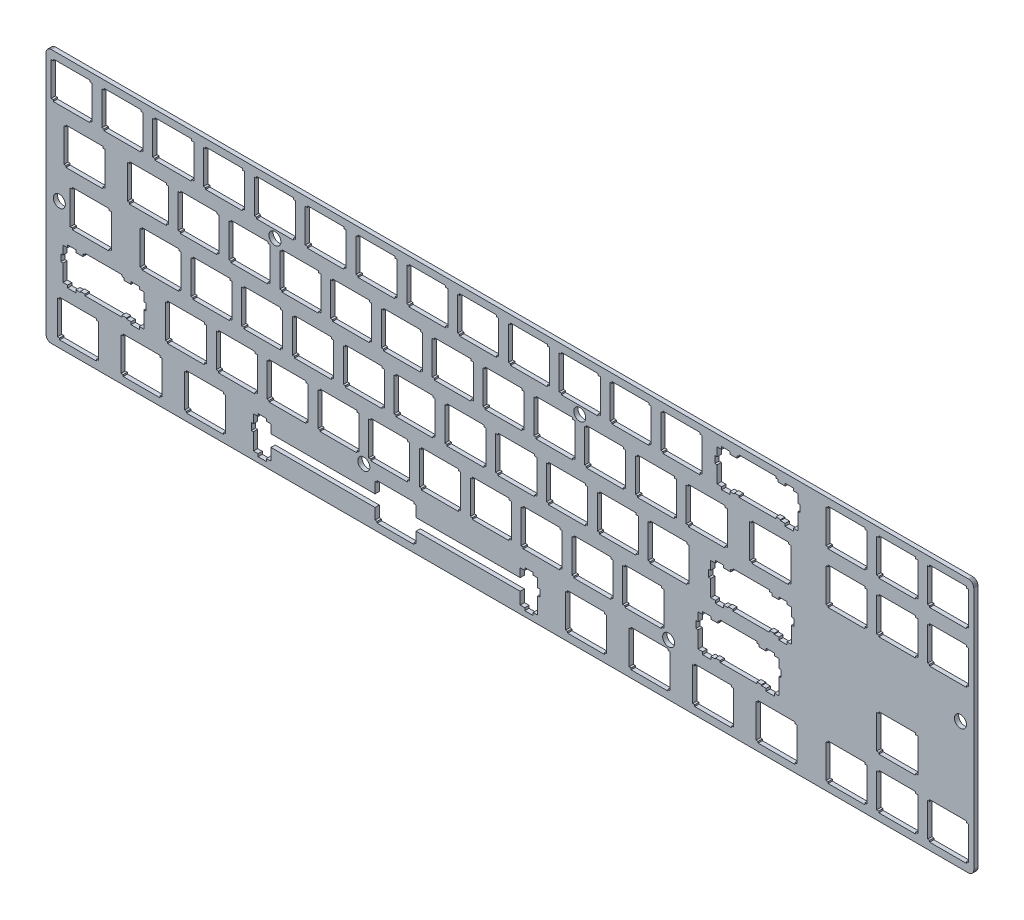
SolidWorks part; units mm, degrees
material "Brass"
ref_plane "Front Plane" through (0, 0, 0) normal (0, 0, 1) x (1, 0, 0)
ref_plane "Top Plane" through (0, 0, 0) normal (0, 1, 0) x (1, 0, 0)
ref_plane "Right Plane" through (0, 0, 0) normal (1, 0, 0) x (0, 0, -1)
sketch "Model" plane through (0, 0, 0) normal (0, 0, 1) x (1, 0, 0)
  line L0 (148.8206, 120.9391) -> (148.8206, 120.3396)
  line L1 (148.8206, 120.3396) -> (148.0216, 120.3396)
  line L2 (148.0216, 120.3396) -> (148.0216, 116.2386)
  line L3 (148.0216, 116.2386) -> (108.9957, 116.2386)
  line L4 (108.9957, 116.2386) -> (108.9957, 119.4687)
  line L5 (108.9957, 119.4687) -> (107.2716, 119.4687)
  line L6 (107.2716, 119.4687) -> (107.2716, 120.3879)
  line L7 (107.2716, 120.3879) -> (104.1711, 120.3879)
  line L8 (104.1711, 120.3879) -> (104.1711, 119.4687)
  line L9 (104.1711, 119.4687) -> (102.4456, 119.4687)
  line L10 (102.4456, 119.4687) -> (102.4456, 116.2386)
  line L11 (102.4456, 116.2386) -> (101.6216, 116.2386)
  line L12 (101.6216, 116.2386) -> (101.6216, 113.6383)
  line L13 (101.6216, 113.6383) -> (102.4456, 113.6383)
  line L14 (102.4456, 113.6383) -> (102.4456, 107.3696)
  line L15 (102.4456, 107.3696) -> (104.1711, 107.3696)
  line L16 (104.1711, 107.3696) -> (104.1711, 106.3884)
  line L17 (104.1711, 106.3884) -> (107.2716, 106.3884)
  line L18 (107.2716, 106.3884) -> (107.2716, 107.3696)
  line L19 (107.2716, 107.3696) -> (108.9957, 107.3696)
  line L20 (108.9957, 107.3696) -> (108.9957, 111.8386)
  line L21 (108.9957, 111.8386) -> (148.0216, 111.8386)
  line L22 (148.0216, 111.8386) -> (148.0216, 107.7389)
  line L23 (148.0216, 107.7389) -> (148.8206, 107.7389)
  line L24 (148.8206, 107.7389) -> (148.8206, 107.1381)
  line L25 (148.8206, 107.1381) -> (162.6206, 107.1381)
  line L26 (162.6206, 107.1381) -> (162.6206, 107.7389)
  line L27 (162.6206, 107.7389) -> (163.4216, 107.7389)
  line L28 (163.4216, 107.7389) -> (163.4216, 111.8386)
  line L29 (163.4216, 111.8386) -> (202.4456, 111.8386)
  line L30 (202.4456, 111.8386) -> (202.4456, 107.3696)
  line L31 (202.4456, 107.3696) -> (204.1716, 107.3696)
  line L32 (204.1716, 107.3696) -> (204.1716, 106.3884)
  line L33 (204.1716, 106.3884) -> (207.2716, 106.3884)
  line L34 (207.2716, 106.3884) -> (207.2716, 107.3696)
  line L35 (207.2716, 107.3696) -> (208.9956, 107.3696)
  line L36 (208.9956, 107.3696) -> (208.9956, 113.6383)
  line L37 (208.9956, 113.6383) -> (209.8206, 113.6383)
  line L38 (209.8206, 113.6383) -> (209.8206, 116.2386)
  line L39 (209.8206, 116.2386) -> (208.9956, 116.2386)
  line L40 (208.9956, 116.2386) -> (208.9956, 119.4687)
  line L41 (208.9956, 119.4687) -> (207.2716, 119.4687)
  line L42 (207.2716, 119.4687) -> (207.2716, 120.3879)
  line L43 (207.2716, 120.3879) -> (204.1716, 120.3879)
  line L44 (204.1716, 120.3879) -> (204.1716, 119.4687)
  line L45 (204.1716, 119.4687) -> (202.4456, 119.4687)
  line L46 (202.4456, 119.4687) -> (202.4456, 116.2386)
  line L47 (202.4456, 116.2386) -> (163.4216, 116.2386)
  line L48 (163.4216, 116.2386) -> (163.4216, 120.3396)
  line L49 (163.4216, 120.3396) -> (162.6206, 120.3396)
  line L50 (162.6206, 120.3396) -> (162.6206, 120.9391)
  line L51 (162.6206, 120.9391) -> (148.8206, 120.9391)
  line L52 (355.9896, 120.9391) -> (355.9896, 120.3396)
  line L53 (355.9896, 120.3396) -> (355.1906, 120.3396)
  line L54 (355.1906, 120.3396) -> (355.1906, 107.7389)
  line L55 (355.1906, 107.7389) -> (355.9896, 107.7389)
  line L56 (355.9896, 107.7389) -> (355.9896, 107.1381)
  line L57 (355.9896, 107.1381) -> (369.7906, 107.1381)
  line L58 (369.7906, 107.1381) -> (369.7906, 107.7389)
  line L59 (369.7906, 107.7389) -> (370.5896, 107.7389)
  line L60 (370.5896, 107.7389) -> (370.5896, 120.3396)
  line L61 (370.5896, 120.3396) -> (369.7906, 120.3396)
  line L62 (369.7906, 120.3396) -> (369.7906, 120.9391)
  line L63 (369.7906, 120.9391) -> (355.9896, 120.9391)
  line L64 (336.9396, 120.9391) -> (336.9396, 120.3396)
  line L65 (336.9396, 120.3396) -> (336.1406, 120.3396)
  line L66 (336.1406, 120.3396) -> (336.1406, 107.7389)
  line L67 (336.1406, 107.7389) -> (336.9396, 107.7389)
  line L68 (336.9396, 107.7389) -> (336.9396, 107.1381)
  line L69 (336.9396, 107.1381) -> (350.7406, 107.1381)
  line L70 (350.7406, 107.1381) -> (350.7406, 107.7389)
  line L71 (350.7406, 107.7389) -> (351.5396, 107.7389)
  line L72 (351.5396, 107.7389) -> (351.5396, 120.3396)
  line L73 (351.5396, 120.3396) -> (350.7406, 120.3396)
  line L74 (350.7406, 120.3396) -> (350.7406, 120.9391)
  line L75 (350.7406, 120.9391) -> (336.9396, 120.9391)
  line L76 (317.8896, 120.9391) -> (317.8896, 120.3396)
  line L77 (317.8896, 120.3396) -> (317.0906, 120.3396)
  line L78 (317.0906, 120.3396) -> (317.0906, 107.7389)
  line L79 (317.0906, 107.7389) -> (317.8896, 107.7389)
  line L80 (317.8896, 107.7389) -> (317.8896, 107.1381)
  line L81 (317.8896, 107.1381) -> (331.6906, 107.1381)
  line L82 (331.6906, 107.1381) -> (331.6906, 107.7389)
  line L83 (331.6906, 107.7389) -> (332.4896, 107.7389)
  line L84 (332.4896, 107.7389) -> (332.4896, 120.3396)
  line L85 (332.4896, 120.3396) -> (331.6906, 120.3396)
  line L86 (331.6906, 120.3396) -> (331.6906, 120.9391)
  line L87 (331.6906, 120.9391) -> (317.8896, 120.9391)
  line L88 (291.6956, 120.9391) -> (291.6956, 120.3396)
  line L89 (291.6956, 120.3396) -> (290.8966, 120.3396)
  line L90 (290.8966, 120.3396) -> (290.8966, 107.7389)
  line L91 (290.8966, 107.7389) -> (291.6956, 107.7389)
  line L92 (291.6956, 107.7389) -> (291.6956, 107.1381)
  line L93 (291.6956, 107.1381) -> (305.4956, 107.1381)
  line L94 (305.4956, 107.1381) -> (305.4956, 107.7389)
  line L95 (305.4956, 107.7389) -> (306.2966, 107.7389)
  line L96 (306.2966, 107.7389) -> (306.2966, 120.3396)
  line L97 (306.2966, 120.3396) -> (305.4956, 120.3396)
  line L98 (305.4956, 120.3396) -> (305.4956, 120.9391)
  line L99 (305.4956, 120.9391) -> (291.6956, 120.9391)
  line L100 (267.8846, 120.9391) -> (267.8846, 120.3396)
  line L101 (267.8846, 120.3396) -> (267.0846, 120.3396)
  line L102 (267.0846, 120.3396) -> (267.0846, 107.7389)
  line L103 (267.0846, 107.7389) -> (267.8846, 107.7389)
  line L104 (267.8846, 107.7389) -> (267.8846, 107.1381)
  line L105 (267.8846, 107.1381) -> (281.6846, 107.1381)
  line L106 (281.6846, 107.1381) -> (281.6846, 107.7389)
  line L107 (281.6846, 107.7389) -> (282.4836, 107.7389)
  line L108 (282.4836, 107.7389) -> (282.4836, 120.3396)
  line L109 (282.4836, 120.3396) -> (281.6846, 120.3396)
  line L110 (281.6846, 120.3396) -> (281.6846, 120.9391)
  line L111 (281.6846, 120.9391) -> (267.8846, 120.9391)
  line L112 (244.0706, 120.9391) -> (244.0706, 120.3396)
  line L113 (244.0706, 120.3396) -> (243.2716, 120.3396)
  line L114 (243.2716, 120.3396) -> (243.2716, 107.7389)
  line L115 (243.2716, 107.7389) -> (244.0706, 107.7389)
  line L116 (244.0706, 107.7389) -> (244.0706, 107.1381)
  line L117 (244.0706, 107.1381) -> (257.8706, 107.1381)
  line L118 (257.8706, 107.1381) -> (257.8706, 107.7389)
  line L119 (257.8706, 107.7389) -> (258.6716, 107.7389)
  line L120 (258.6716, 107.7389) -> (258.6716, 120.3396)
  line L121 (258.6716, 120.3396) -> (257.8706, 120.3396)
  line L122 (257.8706, 120.3396) -> (257.8706, 120.9391)
  line L123 (257.8706, 120.9391) -> (244.0706, 120.9391)
  line L124 (220.2596, 120.9391) -> (220.2596, 120.3396)
  line L125 (220.2596, 120.3396) -> (219.4596, 120.3396)
  line L126 (219.4596, 120.3396) -> (219.4596, 107.7389)
  line L127 (219.4596, 107.7389) -> (220.2596, 107.7389)
  line L128 (220.2596, 107.7389) -> (220.2596, 107.1381)
  line L129 (220.2596, 107.1381) -> (234.0596, 107.1381)
  line L130 (234.0596, 107.1381) -> (234.0596, 107.7389)
  line L131 (234.0596, 107.7389) -> (234.8586, 107.7389)
  line L132 (234.8586, 107.7389) -> (234.8586, 120.3396)
  line L133 (234.8586, 120.3396) -> (234.0596, 120.3396)
  line L134 (234.0596, 120.3396) -> (234.0596, 120.9391)
  line L135 (234.0596, 120.9391) -> (220.2596, 120.9391)
  line L136 (77.3847, 120.9391) -> (77.3847, 120.3396)
  line L137 (77.3847, 120.3396) -> (76.5842, 120.3396)
  line L138 (76.5842, 120.3396) -> (76.5842, 107.7389)
  line L139 (76.5842, 107.7389) -> (77.3847, 107.7389)
  line L140 (77.3847, 107.7389) -> (77.3847, 107.1381)
  line L141 (77.3847, 107.1381) -> (91.1843, 107.1381)
  line L142 (91.1843, 107.1381) -> (91.1843, 107.7389)
  line L143 (91.1843, 107.7389) -> (91.9837, 107.7389)
  line L144 (91.9837, 107.7389) -> (91.9837, 120.3396)
  line L145 (91.9837, 120.3396) -> (91.1843, 120.3396)
  line L146 (91.1843, 120.3396) -> (91.1843, 120.9391)
  line L147 (91.1843, 120.9391) -> (77.3847, 120.9391)
  line L148 (53.5708, 120.9391) -> (53.5708, 120.3396)
  line L149 (53.5708, 120.3396) -> (52.7716, 120.3396)
  line L150 (52.7716, 120.3396) -> (52.7716, 107.7389)
  line L151 (52.7716, 107.7389) -> (53.5708, 107.7389)
  line L152 (53.5708, 107.7389) -> (53.5708, 107.1381)
  line L153 (53.5708, 107.1381) -> (67.3704, 107.1381)
  line L154 (67.3704, 107.1381) -> (67.3704, 107.7389)
  line L155 (67.3704, 107.7389) -> (68.1712, 107.7389)
  line L156 (68.1712, 107.7389) -> (68.1712, 120.3396)
  line L157 (68.1712, 120.3396) -> (67.3704, 120.3396)
  line L158 (67.3704, 120.3396) -> (67.3704, 120.9391)
  line L159 (67.3704, 120.9391) -> (53.5708, 120.9391)
  line L160 (29.7597, 120.9391) -> (29.7597, 120.3396)
  line L161 (29.7597, 120.3396) -> (28.959, 120.3396)
  line L162 (28.959, 120.3396) -> (28.959, 107.7389)
  line L163 (28.959, 107.7389) -> (29.7597, 107.7389)
  line L164 (29.7597, 107.7389) -> (29.7597, 107.1381)
  line L165 (29.7597, 107.1381) -> (43.5594, 107.1381)
  line L166 (43.5594, 107.1381) -> (43.5594, 107.7389)
  line L167 (43.5594, 107.7389) -> (44.3586, 107.7389)
  line L168 (44.3586, 107.7389) -> (44.3586, 120.3396)
  line L169 (44.3586, 120.3396) -> (43.5594, 120.3396)
  line L170 (43.5594, 120.3396) -> (43.5594, 120.9391)
  line L171 (43.5594, 120.9391) -> (29.7597, 120.9391)
  line L172 (277.4086, 139.9906) -> (277.4086, 139.3898)
  line L173 (277.4086, 139.3898) -> (276.6096, 139.3898)
  line L174 (276.6096, 139.3898) -> (276.6096, 138.5187)
  line L175 (275.6846, 138.5187) -> (273.9596, 138.5187)
  line L176 (273.9596, 138.5187) -> (273.9596, 139.4378)
  line L177 (273.9596, 139.4378) -> (270.8586, 139.4378)
  line L178 (270.8586, 139.4378) -> (270.8586, 138.5187)
  line L179 (270.8586, 138.5187) -> (269.1346, 138.5187)
  line L180 (269.1346, 138.5187) -> (269.1346, 135.2886)
  line L181 (269.1346, 135.2886) -> (268.3086, 135.2886)
  line L182 (268.3086, 135.2886) -> (268.3086, 132.6882)
  line L183 (268.3086, 132.6882) -> (269.1346, 132.6882)
  line L184 (269.1346, 132.6882) -> (269.1346, 126.4182)
  line L185 (269.1346, 126.4182) -> (270.8586, 126.4182)
  line L186 (270.8586, 126.4182) -> (270.8586, 125.4384)
  line L187 (270.8586, 125.4384) -> (273.9596, 125.4384)
  line L188 (273.9596, 125.4384) -> (273.9596, 126.4182)
  line L189 (273.9596, 126.4182) -> (275.6846, 126.4182)
  line L190 (275.6846, 126.4182) -> (275.6846, 126.7888)
  line L191 (276.6096, 126.7888) -> (277.4086, 126.7888)
  line L192 (277.4086, 126.7888) -> (277.4086, 126.188)
  line L193 (277.4086, 126.188) -> (291.2096, 126.188)
  line L194 (291.2096, 126.188) -> (291.2096, 126.7888)
  line L195 (291.2096, 126.7888) -> (292.0086, 126.7888)
  line L196 (292.9346, 126.7888) -> (292.9346, 126.4182)
  line L197 (292.9346, 126.4182) -> (294.6586, 126.4182)
  line L198 (294.6586, 126.4182) -> (294.6586, 125.4384)
  line L199 (294.6586, 125.4384) -> (297.7596, 125.4384)
  line L200 (297.7596, 125.4384) -> (297.7596, 126.4182)
  line L201 (297.7596, 126.4182) -> (299.4846, 126.4182)
  line L202 (299.4846, 126.4182) -> (299.4846, 132.6882)
  line L203 (299.4846, 132.6882) -> (300.3086, 132.6882)
  line L204 (300.3086, 132.6882) -> (300.3086, 135.2886)
  line L205 (300.3086, 135.2886) -> (299.4846, 135.2886)
  line L206 (299.4846, 135.2886) -> (299.4846, 138.5187)
  line L207 (299.4846, 138.5187) -> (297.7596, 138.5187)
  line L208 (297.7596, 138.5187) -> (297.7596, 139.4378)
  line L209 (297.7596, 139.4378) -> (294.6586, 139.4378)
  line L210 (294.6586, 139.4378) -> (294.6586, 138.5187)
  line L211 (294.6586, 138.5187) -> (292.9346, 138.5187)
  line L212 (292.0086, 138.5187) -> (292.0086, 139.3898)
  line L213 (292.0086, 139.3898) -> (291.2096, 139.3898)
  line L214 (291.2096, 139.3898) -> (291.2096, 139.9906)
  line L215 (291.2096, 139.9906) -> (277.4086, 139.9906)
  line L216 (39.2847, 139.9906) -> (39.2847, 139.3898)
  line L217 (39.2847, 139.3898) -> (38.4841, 139.3898)
  line L218 (38.4841, 139.3898) -> (38.4841, 138.5187)
  line L219 (299.1536, 195.6688) -> (300.0786, 195.6688)
  line L220 (296.7716, 157.5688) -> (297.6956, 157.5688)
  line L221 (37.5594, 138.5187) -> (35.8341, 138.5187)
  line L222 (35.8341, 138.5187) -> (35.8341, 139.4378)
  line L223 (35.8341, 139.4378) -> (32.7335, 139.4378)
  line L224 (32.7335, 139.4378) -> (32.7335, 138.5187)
  line L225 (32.7335, 138.5187) -> (31.0095, 138.5187)
  line L226 (31.0095, 138.5187) -> (31.0095, 135.2886)
  line L227 (31.0095, 135.2886) -> (30.1841, 135.2886)
  line L228 (30.1841, 135.2886) -> (30.1841, 132.6882)
  line L229 (30.1841, 132.6882) -> (31.0095, 132.6882)
  line L230 (31.0095, 132.6882) -> (31.0095, 126.4182)
  line L231 (31.0095, 126.4182) -> (32.7335, 126.4182)
  line L232 (32.7335, 126.4182) -> (32.7335, 125.4384)
  line L233 (32.7335, 125.4384) -> (35.8341, 125.4384)
  line L234 (35.8341, 125.4384) -> (35.8341, 126.4182)
  line L235 (35.8341, 126.4182) -> (37.5594, 126.4182)
  line L236 (37.5594, 126.4182) -> (37.5594, 126.7888)
  line L237 (292.0086, 138.5187) -> (292.9346, 138.5187)
  line L238 (38.4841, 126.7888) -> (39.2847, 126.7888)
  line L239 (39.2847, 126.7888) -> (39.2847, 126.188)
  line L240 (39.2847, 126.188) -> (53.0844, 126.188)
  line L241 (53.0844, 126.188) -> (53.0844, 126.7888)
  line L242 (53.0844, 126.7888) -> (53.8836, 126.7888)
  line L243 (54.8097, 126.7888) -> (54.8097, 126.4182)
  line L244 (54.8097, 126.4182) -> (56.5336, 126.4182)
  line L245 (56.5336, 126.4182) -> (56.5336, 125.4384)
  line L246 (56.5336, 125.4384) -> (59.6342, 125.4384)
  line L247 (59.6342, 125.4384) -> (59.6342, 126.4182)
  line L248 (59.6342, 126.4182) -> (61.3594, 126.4182)
  line L249 (61.3594, 126.4182) -> (61.3594, 132.6882)
  line L250 (61.3594, 132.6882) -> (62.1835, 132.6882)
  line L251 (62.1835, 132.6882) -> (62.1835, 135.2886)
  line L252 (62.1835, 135.2886) -> (61.3594, 135.2886)
  line L253 (61.3594, 135.2886) -> (61.3594, 138.5187)
  line L254 (61.3594, 138.5187) -> (59.6342, 138.5187)
  line L255 (59.6342, 138.5187) -> (59.6342, 139.4378)
  line L256 (59.6342, 139.4378) -> (56.5336, 139.4378)
  line L257 (56.5336, 139.4378) -> (56.5336, 138.5187)
  line L258 (56.5336, 138.5187) -> (54.8097, 138.5187)
  line L259 (53.8836, 138.5187) -> (53.8836, 139.3898)
  line L260 (53.8836, 139.3898) -> (53.0844, 139.3898)
  line L261 (53.0844, 139.3898) -> (53.0844, 139.9906)
  line L262 (53.0844, 139.9906) -> (39.2847, 139.9906)
  line L263 (336.9396, 139.9906) -> (336.9396, 139.3898)
  line L264 (336.9396, 139.3898) -> (336.1406, 139.3898)
  line L265 (336.1406, 139.3898) -> (336.1406, 126.7888)
  line L266 (336.1406, 126.7888) -> (336.9396, 126.7888)
  line L267 (336.9396, 126.7888) -> (336.9396, 126.188)
  line L268 (336.9396, 126.188) -> (350.7406, 126.188)
  line L269 (350.7406, 126.188) -> (350.7406, 126.7888)
  line L270 (350.7406, 126.7888) -> (351.5396, 126.7888)
  line L271 (351.5396, 126.7888) -> (351.5396, 139.3898)
  line L272 (351.5396, 139.3898) -> (350.7406, 139.3898)
  line L273 (350.7406, 139.3898) -> (350.7406, 139.9906)
  line L274 (350.7406, 139.9906) -> (336.9396, 139.9906)
  line L275 (241.6896, 139.9906) -> (241.6896, 139.3898)
  line L276 (241.6896, 139.3898) -> (240.8906, 139.3898)
  line L277 (240.8906, 139.3898) -> (240.8906, 126.7888)
  line L278 (240.8906, 126.7888) -> (241.6896, 126.7888)
  line L279 (241.6896, 126.7888) -> (241.6896, 126.188)
  line L280 (241.6896, 126.188) -> (255.4906, 126.188)
  line L281 (255.4906, 126.188) -> (255.4906, 126.7888)
  line L282 (255.4906, 126.7888) -> (256.2896, 126.7888)
  line L283 (256.2896, 126.7888) -> (256.2896, 139.3898)
  line L284 (256.2896, 139.3898) -> (255.4906, 139.3898)
  line L285 (255.4906, 139.3898) -> (255.4906, 139.9906)
  line L286 (255.4906, 139.9906) -> (241.6896, 139.9906)
  line L287 (222.6396, 139.9906) -> (222.6396, 139.3898)
  line L288 (222.6396, 139.3898) -> (221.8406, 139.3898)
  line L289 (221.8406, 139.3898) -> (221.8406, 126.7888)
  line L290 (221.8406, 126.7888) -> (222.6396, 126.7888)
  line L291 (222.6396, 126.7888) -> (222.6396, 126.188)
  line L292 (222.6396, 126.188) -> (236.4406, 126.188)
  line L293 (236.4406, 126.188) -> (236.4406, 126.7888)
  line L294 (236.4406, 126.7888) -> (237.2396, 126.7888)
  line L295 (237.2396, 126.7888) -> (237.2396, 139.3898)
  line L296 (237.2396, 139.3898) -> (236.4406, 139.3898)
  line L297 (236.4406, 139.3898) -> (236.4406, 139.9906)
  line L298 (236.4406, 139.9906) -> (222.6396, 139.9906)
  line L299 (203.5896, 139.9906) -> (203.5896, 139.3898)
  line L300 (203.5896, 139.3898) -> (202.7906, 139.3898)
  line L301 (202.7906, 139.3898) -> (202.7906, 126.7888)
  line L302 (202.7906, 126.7888) -> (203.5896, 126.7888)
  line L303 (203.5896, 126.7888) -> (203.5896, 126.188)
  line L304 (203.5896, 126.188) -> (217.3906, 126.188)
  line L305 (217.3906, 126.188) -> (217.3906, 126.7888)
  line L306 (217.3906, 126.7888) -> (218.1896, 126.7888)
  line L307 (218.1896, 126.7888) -> (218.1896, 139.3898)
  line L308 (218.1896, 139.3898) -> (217.3906, 139.3898)
  line L309 (217.3906, 139.3898) -> (217.3906, 139.9906)
  line L310 (217.3906, 139.9906) -> (203.5896, 139.9906)
  line L311 (184.5396, 139.9906) -> (184.5396, 139.3898)
  line L312 (184.5396, 139.3898) -> (183.7406, 139.3898)
  line L313 (183.7406, 139.3898) -> (183.7406, 126.7888)
  line L314 (183.7406, 126.7888) -> (184.5396, 126.7888)
  line L315 (184.5396, 126.7888) -> (184.5396, 126.188)
  line L316 (184.5396, 126.188) -> (198.3406, 126.188)
  line L317 (198.3406, 126.188) -> (198.3406, 126.7888)
  line L318 (198.3406, 126.7888) -> (199.1396, 126.7888)
  line L319 (199.1396, 126.7888) -> (199.1396, 139.3898)
  line L320 (199.1396, 139.3898) -> (198.3406, 139.3898)
  line L321 (198.3406, 139.3898) -> (198.3406, 139.9906)
  line L322 (198.3406, 139.9906) -> (184.5396, 139.9906)
  line L323 (165.4896, 139.9906) -> (165.4896, 139.3898)
  line L324 (165.4896, 139.3898) -> (164.6906, 139.3898)
  line L325 (164.6906, 139.3898) -> (164.6906, 126.7888)
  line L326 (164.6906, 126.7888) -> (165.4896, 126.7888)
  line L327 (165.4896, 126.7888) -> (165.4896, 126.188)
  line L328 (165.4896, 126.188) -> (179.2906, 126.188)
  line L329 (179.2906, 126.188) -> (179.2906, 126.7888)
  line L330 (179.2906, 126.7888) -> (180.0896, 126.7888)
  line L331 (180.0896, 126.7888) -> (180.0896, 139.3898)
  line L332 (180.0896, 139.3898) -> (179.2906, 139.3898)
  line L333 (179.2906, 139.3898) -> (179.2906, 139.9906)
  line L334 (179.2906, 139.9906) -> (165.4896, 139.9906)
  line L335 (146.4396, 139.9906) -> (146.4396, 139.3898)
  line L336 (146.4396, 139.3898) -> (145.6406, 139.3898)
  line L337 (145.6406, 139.3898) -> (145.6406, 126.7888)
  line L338 (145.6406, 126.7888) -> (146.4396, 126.7888)
  line L339 (146.4396, 126.7888) -> (146.4396, 126.188)
  line L340 (146.4396, 126.188) -> (160.2406, 126.188)
  line L341 (160.2406, 126.188) -> (160.2406, 126.7888)
  line L342 (160.2406, 126.7888) -> (161.0396, 126.7888)
  line L343 (161.0396, 126.7888) -> (161.0396, 139.3898)
  line L344 (161.0396, 139.3898) -> (160.2406, 139.3898)
  line L345 (160.2406, 139.3898) -> (160.2406, 139.9906)
  line L346 (160.2406, 139.9906) -> (146.4396, 139.9906)
  line L347 (127.3896, 139.9906) -> (127.3896, 139.3898)
  line L348 (127.3896, 139.3898) -> (126.5906, 139.3898)
  line L349 (126.5906, 139.3898) -> (126.5906, 126.7888)
  line L350 (126.5906, 126.7888) -> (127.3896, 126.7888)
  line L351 (127.3896, 126.7888) -> (127.3896, 126.188)
  line L352 (127.3896, 126.188) -> (141.1906, 126.188)
  line L353 (141.1906, 126.188) -> (141.1906, 126.7888)
  line L354 (141.1906, 126.7888) -> (141.9896, 126.7888)
  line L355 (141.9896, 126.7888) -> (141.9896, 139.3898)
  line L356 (141.9896, 139.3898) -> (141.1906, 139.3898)
  line L357 (141.1906, 139.3898) -> (141.1906, 139.9906)
  line L358 (141.1906, 139.9906) -> (127.3896, 139.9906)
  line L359 (108.3395, 139.9906) -> (108.3395, 139.3898)
  line L360 (108.3395, 139.3898) -> (107.5405, 139.3898)
  line L361 (107.5405, 139.3898) -> (107.5405, 126.7888)
  line L362 (107.5405, 126.7888) -> (108.3395, 126.7888)
  line L363 (108.3395, 126.7888) -> (108.3395, 126.188)
  line L364 (108.3395, 126.188) -> (122.1405, 126.188)
  line L365 (122.1405, 126.188) -> (122.1405, 126.7888)
  line L366 (122.1405, 126.7888) -> (122.9399, 126.7888)
  line L367 (122.9399, 126.7888) -> (122.9399, 139.3898)
  line L368 (122.9399, 139.3898) -> (122.1405, 139.3898)
  line L369 (122.1405, 139.3898) -> (122.1405, 139.9906)
  line L370 (122.1405, 139.9906) -> (108.3395, 139.9906)
  line L371 (89.2895, 139.9906) -> (89.2895, 139.3898)
  line L372 (89.2895, 139.3898) -> (88.4905, 139.3898)
  line L373 (88.4905, 139.3898) -> (88.4905, 126.7888)
  line L374 (88.4905, 126.7888) -> (89.2895, 126.7888)
  line L375 (89.2895, 126.7888) -> (89.2895, 126.188)
  line L376 (89.2895, 126.188) -> (103.0905, 126.188)
  line L377 (103.0905, 126.188) -> (103.0905, 126.7888)
  line L378 (103.0905, 126.7888) -> (103.8899, 126.7888)
  line L379 (103.8899, 126.7888) -> (103.8899, 139.3898)
  line L380 (103.8899, 139.3898) -> (103.0905, 139.3898)
  line L381 (103.0905, 139.3898) -> (103.0905, 139.9906)
  line L382 (103.0905, 139.9906) -> (89.2895, 139.9906)
  line L383 (70.2395, 139.9906) -> (70.2395, 139.3898)
  line L384 (70.2395, 139.3898) -> (69.4405, 139.3898)
  line L385 (69.4405, 139.3898) -> (69.4405, 126.7888)
  line L386 (69.4405, 126.7888) -> (70.2395, 126.7888)
  line L387 (70.2395, 126.7888) -> (70.2395, 126.188)
  line L388 (70.2395, 126.188) -> (84.0405, 126.188)
  line L389 (84.0405, 126.188) -> (84.0405, 126.7888)
  line L390 (84.0405, 126.7888) -> (84.8399, 126.7888)
  line L391 (84.8399, 126.7888) -> (84.8399, 139.3898)
  line L392 (84.8399, 139.3898) -> (84.0405, 139.3898)
  line L393 (84.0405, 139.3898) -> (84.0405, 139.9906)
  line L394 (84.0405, 139.9906) -> (70.2395, 139.9906)
  line L395 (282.1706, 159.0392) -> (282.1706, 158.4384)
  line L396 (282.1706, 158.4384) -> (281.3716, 158.4384)
  line L397 (281.3716, 158.4384) -> (281.3716, 157.5688)
  line L398 (280.4456, 157.5688) -> (278.7206, 157.5688)
  line L399 (278.7206, 157.5688) -> (278.7206, 158.4892)
  line L400 (278.7206, 158.4892) -> (275.6206, 158.4892)
  line L401 (275.6206, 158.4892) -> (275.6206, 157.5688)
  line L402 (275.6206, 157.5688) -> (273.8956, 157.5688)
  line L403 (273.8956, 157.5688) -> (273.8956, 154.3387)
  line L404 (273.8956, 154.3387) -> (273.0716, 154.3387)
  line L405 (273.0716, 154.3387) -> (273.0716, 151.7395)
  line L406 (273.0716, 151.7395) -> (273.8956, 151.7395)
  line L407 (273.8956, 151.7395) -> (273.8956, 145.4696)
  line L408 (273.8956, 145.4696) -> (275.6206, 145.4696)
  line L409 (275.6206, 145.4696) -> (275.6206, 144.4885)
  line L410 (275.6206, 144.4885) -> (278.7206, 144.4885)
  line L411 (278.7206, 144.4885) -> (278.7206, 145.4696)
  line L412 (278.7206, 145.4696) -> (280.4456, 145.4696)
  line L413 (280.4456, 145.4696) -> (280.4456, 145.8389)
  line L414 (281.3716, 145.8389) -> (282.1706, 145.8389)
  line L415 (282.1706, 145.8389) -> (282.1706, 145.2395)
  line L416 (282.1706, 145.2395) -> (295.9706, 145.2395)
  line L417 (295.9706, 145.2395) -> (295.9706, 145.8389)
  line L418 (295.9706, 145.8389) -> (296.7716, 145.8389)
  line L419 (297.6956, 145.8389) -> (297.6956, 145.4696)
  line L420 (297.6956, 145.4696) -> (299.4216, 145.4696)
  line L421 (299.4216, 145.4696) -> (299.4216, 144.4885)
  line L422 (299.4216, 144.4885) -> (302.5216, 144.4885)
  line L423 (302.5216, 144.4885) -> (302.5216, 145.4696)
  line L424 (302.5216, 145.4696) -> (304.2456, 145.4696)
  line L425 (304.2456, 145.4696) -> (304.2456, 151.7395)
  line L426 (304.2456, 151.7395) -> (305.0706, 151.7395)
  line L427 (305.0706, 151.7395) -> (305.0706, 154.3387)
  line L428 (305.0706, 154.3387) -> (304.2456, 154.3387)
  line L429 (304.2456, 154.3387) -> (304.2456, 157.5688)
  line L430 (304.2456, 157.5688) -> (302.5216, 157.5688)
  line L431 (302.5216, 157.5688) -> (302.5216, 158.4892)
  line L432 (302.5216, 158.4892) -> (299.4216, 158.4892)
  line L433 (299.4216, 158.4892) -> (299.4216, 157.5688)
  line L434 (299.4216, 157.5688) -> (297.6956, 157.5688)
  line L435 (296.7716, 157.5688) -> (296.7716, 158.4384)
  line L436 (296.7716, 158.4384) -> (295.9706, 158.4384)
  line L437 (295.9706, 158.4384) -> (295.9706, 159.0392)
  line L438 (295.9706, 159.0392) -> (282.1706, 159.0392)
  line L439 (251.2146, 159.0392) -> (251.2146, 158.4384)
  line L440 (251.2146, 158.4384) -> (250.4156, 158.4384)
  line L441 (250.4156, 158.4384) -> (250.4156, 145.8389)
  line L442 (250.4156, 145.8389) -> (251.2146, 145.8389)
  line L443 (251.2146, 145.8389) -> (251.2146, 145.2395)
  line L444 (251.2146, 145.2395) -> (265.0156, 145.2395)
  line L445 (265.0156, 145.2395) -> (265.0156, 145.8389)
  line L446 (265.0156, 145.8389) -> (265.8146, 145.8389)
  line L447 (265.8146, 145.8389) -> (265.8146, 158.4384)
  line L448 (265.8146, 158.4384) -> (265.0156, 158.4384)
  line L449 (265.0156, 158.4384) -> (265.0156, 159.0392)
  line L450 (265.0156, 159.0392) -> (251.2146, 159.0392)
  line L451 (232.1646, 159.0392) -> (232.1646, 158.4384)
  line L452 (232.1646, 158.4384) -> (231.3656, 158.4384)
  line L453 (231.3656, 158.4384) -> (231.3656, 145.8389)
  line L454 (231.3656, 145.8389) -> (232.1646, 145.8389)
  line L455 (232.1646, 145.8389) -> (232.1646, 145.2395)
  line L456 (232.1646, 145.2395) -> (245.9656, 145.2395)
  line L457 (245.9656, 145.2395) -> (245.9656, 145.8389)
  line L458 (245.9656, 145.8389) -> (246.7646, 145.8389)
  line L459 (246.7646, 145.8389) -> (246.7646, 158.4384)
  line L460 (246.7646, 158.4384) -> (245.9656, 158.4384)
  line L461 (245.9656, 158.4384) -> (245.9656, 159.0392)
  line L462 (245.9656, 159.0392) -> (232.1646, 159.0392)
  line L463 (213.1146, 159.0392) -> (213.1146, 158.4384)
  line L464 (213.1146, 158.4384) -> (212.3156, 158.4384)
  line L465 (212.3156, 158.4384) -> (212.3156, 145.8389)
  line L466 (212.3156, 145.8389) -> (213.1146, 145.8389)
  line L467 (213.1146, 145.8389) -> (213.1146, 145.2395)
  line L468 (213.1146, 145.2395) -> (226.9156, 145.2395)
  line L469 (226.9156, 145.2395) -> (226.9156, 145.8389)
  line L470 (226.9156, 145.8389) -> (227.7146, 145.8389)
  line L471 (227.7146, 145.8389) -> (227.7146, 158.4384)
  line L472 (227.7146, 158.4384) -> (226.9156, 158.4384)
  line L473 (226.9156, 158.4384) -> (226.9156, 159.0392)
  line L474 (226.9156, 159.0392) -> (213.1146, 159.0392)
  line L475 (194.0646, 159.0392) -> (194.0646, 158.4384)
  line L476 (194.0646, 158.4384) -> (193.2656, 158.4384)
  line L477 (193.2656, 158.4384) -> (193.2656, 145.8389)
  line L478 (193.2656, 145.8389) -> (194.0646, 145.8389)
  line L479 (194.0646, 145.8389) -> (194.0646, 145.2395)
  line L480 (194.0646, 145.2395) -> (207.8656, 145.2395)
  line L481 (207.8656, 145.2395) -> (207.8656, 145.8389)
  line L482 (207.8656, 145.8389) -> (208.6646, 145.8389)
  line L483 (208.6646, 145.8389) -> (208.6646, 158.4384)
  line L484 (208.6646, 158.4384) -> (207.8656, 158.4384)
  line L485 (207.8656, 158.4384) -> (207.8656, 159.0392)
  line L486 (207.8656, 159.0392) -> (194.0646, 159.0392)
  line L487 (175.0146, 159.0392) -> (175.0146, 158.4384)
  line L488 (175.0146, 158.4384) -> (174.2156, 158.4384)
  line L489 (174.2156, 158.4384) -> (174.2156, 145.8389)
  line L490 (174.2156, 145.8389) -> (175.0146, 145.8389)
  line L491 (175.0146, 145.8389) -> (175.0146, 145.2395)
  line L492 (175.0146, 145.2395) -> (188.8156, 145.2395)
  line L493 (188.8156, 145.2395) -> (188.8156, 145.8389)
  line L494 (188.8156, 145.8389) -> (189.6146, 145.8389)
  line L495 (189.6146, 145.8389) -> (189.6146, 158.4384)
  line L496 (189.6146, 158.4384) -> (188.8156, 158.4384)
  line L497 (188.8156, 158.4384) -> (188.8156, 159.0392)
  line L498 (188.8156, 159.0392) -> (175.0146, 159.0392)
  line L499 (155.9646, 159.0392) -> (155.9646, 158.4384)
  line L500 (155.9646, 158.4384) -> (155.1656, 158.4384)
  line L501 (155.1656, 158.4384) -> (155.1656, 145.8389)
  line L502 (155.1656, 145.8389) -> (155.9646, 145.8389)
  line L503 (155.9646, 145.8389) -> (155.9646, 145.2395)
  line L504 (155.9646, 145.2395) -> (169.7656, 145.2395)
  line L505 (169.7656, 145.2395) -> (169.7656, 145.8389)
  line L506 (169.7656, 145.8389) -> (170.5646, 145.8389)
  line L507 (170.5646, 145.8389) -> (170.5646, 158.4384)
  line L508 (170.5646, 158.4384) -> (169.7656, 158.4384)
  line L509 (169.7656, 158.4384) -> (169.7656, 159.0392)
  line L510 (169.7656, 159.0392) -> (155.9646, 159.0392)
  line L511 (136.9146, 159.0392) -> (136.9146, 158.4384)
  line L512 (136.9146, 158.4384) -> (136.1156, 158.4384)
  line L513 (136.1156, 158.4384) -> (136.1156, 145.8389)
  line L514 (136.1156, 145.8389) -> (136.9146, 145.8389)
  line L515 (136.9146, 145.8389) -> (136.9146, 145.2395)
  line L516 (136.9146, 145.2395) -> (150.7156, 145.2395)
  line L517 (150.7156, 145.2395) -> (150.7156, 145.8389)
  line L518 (150.7156, 145.8389) -> (151.5146, 145.8389)
  line L519 (151.5146, 145.8389) -> (151.5146, 158.4384)
  line L520 (151.5146, 158.4384) -> (150.7156, 158.4384)
  line L521 (150.7156, 158.4384) -> (150.7156, 159.0392)
  line L522 (150.7156, 159.0392) -> (136.9146, 159.0392)
  line L523 (117.8645, 159.0392) -> (117.8645, 158.4384)
  line L524 (117.8645, 158.4384) -> (117.0655, 158.4384)
  line L525 (117.0655, 158.4384) -> (117.0655, 145.8389)
  line L526 (117.0655, 145.8389) -> (117.8645, 145.8389)
  line L527 (117.8645, 145.8389) -> (117.8645, 145.2395)
  line L528 (117.8645, 145.2395) -> (131.6656, 145.2395)
  line L529 (131.6656, 145.2395) -> (131.6656, 145.8389)
  line L530 (131.6656, 145.8389) -> (132.4646, 145.8389)
  line L531 (132.4646, 145.8389) -> (132.4646, 158.4384)
  line L532 (132.4646, 158.4384) -> (131.6656, 158.4384)
  line L533 (131.6656, 158.4384) -> (131.6656, 159.0392)
  line L534 (131.6656, 159.0392) -> (117.8645, 159.0392)
  line L535 (98.8145, 159.0392) -> (98.8145, 158.4384)
  line L536 (98.8145, 158.4384) -> (98.0155, 158.4384)
  line L537 (98.0155, 158.4384) -> (98.0155, 145.8389)
  line L538 (98.0155, 145.8389) -> (98.8145, 145.8389)
  line L539 (98.8145, 145.8389) -> (98.8145, 145.2395)
  line L540 (98.8145, 145.2395) -> (112.6155, 145.2395)
  line L541 (112.6155, 145.2395) -> (112.6155, 145.8389)
  line L542 (112.6155, 145.8389) -> (113.4149, 145.8389)
  line L543 (113.4149, 145.8389) -> (113.4149, 158.4384)
  line L544 (113.4149, 158.4384) -> (112.6155, 158.4384)
  line L545 (112.6155, 158.4384) -> (112.6155, 159.0392)
  line L546 (112.6155, 159.0392) -> (98.8145, 159.0392)
  line L547 (79.7645, 159.0392) -> (79.7645, 158.4384)
  line L548 (79.7645, 158.4384) -> (78.9655, 158.4384)
  line L549 (78.9655, 158.4384) -> (78.9655, 145.8389)
  line L550 (78.9655, 145.8389) -> (79.7645, 145.8389)
  line L551 (79.7645, 145.8389) -> (79.7645, 145.2395)
  line L552 (79.7645, 145.2395) -> (93.5655, 145.2395)
  line L553 (93.5655, 145.2395) -> (93.5655, 145.8389)
  line L554 (93.5655, 145.8389) -> (94.3649, 145.8389)
  line L555 (94.3649, 145.8389) -> (94.3649, 158.4384)
  line L556 (94.3649, 158.4384) -> (93.5655, 158.4384)
  line L557 (93.5655, 158.4384) -> (93.5655, 159.0392)
  line L558 (93.5655, 159.0392) -> (79.7645, 159.0392)
  line L559 (60.7145, 159.0392) -> (60.7145, 158.4384)
  line L560 (60.7145, 158.4384) -> (59.9155, 158.4384)
  line L561 (59.9155, 158.4384) -> (59.9155, 145.8389)
  line L562 (59.9155, 145.8389) -> (60.7145, 145.8389)
  line L563 (60.7145, 145.8389) -> (60.7145, 145.2395)
  line L564 (60.7145, 145.2395) -> (74.5155, 145.2395)
  line L565 (74.5155, 145.2395) -> (74.5155, 145.8389)
  line L566 (74.5155, 145.8389) -> (75.3149, 145.8389)
  line L567 (75.3149, 145.8389) -> (75.3149, 158.4384)
  line L568 (75.3149, 158.4384) -> (74.5155, 158.4384)
  line L569 (74.5155, 158.4384) -> (74.5155, 159.0392)
  line L570 (74.5155, 159.0392) -> (60.7145, 159.0392)
  line L571 (34.5208, 159.0392) -> (34.5208, 158.4384)
  line L572 (34.5208, 158.4384) -> (33.7215, 158.4384)
  line L573 (33.7215, 158.4384) -> (33.7215, 145.8389)
  line L574 (33.7215, 145.8389) -> (34.5208, 145.8389)
  line L575 (34.5208, 145.8389) -> (34.5208, 145.2395)
  line L576 (34.5208, 145.2395) -> (48.3205, 145.2395)
  line L577 (48.3205, 145.2395) -> (48.3205, 145.8389)
  line L578 (48.3205, 145.8389) -> (49.1211, 145.8389)
  line L579 (49.1211, 145.8389) -> (49.1211, 158.4384)
  line L580 (49.1211, 158.4384) -> (48.3205, 158.4384)
  line L581 (48.3205, 158.4384) -> (48.3205, 159.0392)
  line L582 (48.3205, 159.0392) -> (34.5208, 159.0392)
  line L583 (355.9896, 178.0877) -> (355.9896, 177.4898)
  line L584 (355.9896, 177.4898) -> (355.1906, 177.4898)
  line L585 (355.1906, 177.4898) -> (355.1906, 164.8889)
  line L586 (355.1906, 164.8889) -> (355.9896, 164.8889)
  line L587 (355.9896, 164.8889) -> (355.9896, 164.2895)
  line L588 (355.9896, 164.2895) -> (369.7906, 164.2895)
  line L589 (369.7906, 164.2895) -> (369.7906, 164.8889)
  line L590 (369.7906, 164.8889) -> (370.5896, 164.8889)
  line L591 (370.5896, 164.8889) -> (370.5896, 177.4898)
  line L592 (370.5896, 177.4898) -> (369.7906, 177.4898)
  line L593 (369.7906, 177.4898) -> (369.7906, 178.0877)
  line L594 (369.7906, 178.0877) -> (355.9896, 178.0877)
  line L595 (336.9396, 178.0877) -> (336.9396, 177.4898)
  line L596 (336.9396, 177.4898) -> (336.1406, 177.4898)
  line L597 (336.1406, 177.4898) -> (336.1406, 164.8889)
  line L598 (336.1406, 164.8889) -> (336.9396, 164.8889)
  line L599 (336.9396, 164.8889) -> (336.9396, 164.2895)
  line L600 (336.9396, 164.2895) -> (350.7406, 164.2895)
  line L601 (350.7406, 164.2895) -> (350.7406, 164.8889)
  line L602 (350.7406, 164.8889) -> (351.5396, 164.8889)
  line L603 (351.5396, 164.8889) -> (351.5396, 177.4898)
  line L604 (351.5396, 177.4898) -> (350.7406, 177.4898)
  line L605 (350.7406, 177.4898) -> (350.7406, 178.0877)
  line L606 (350.7406, 178.0877) -> (336.9396, 178.0877)
  line L607 (317.8896, 178.0877) -> (317.8896, 177.4898)
  line L608 (317.8896, 177.4898) -> (317.0906, 177.4898)
  line L609 (317.0906, 177.4898) -> (317.0906, 164.8889)
  line L610 (317.0906, 164.8889) -> (317.8896, 164.8889)
  line L611 (317.8896, 164.8889) -> (317.8896, 164.2895)
  line L612 (317.8896, 164.2895) -> (331.6906, 164.2895)
  line L613 (331.6906, 164.2895) -> (331.6906, 164.8889)
  line L614 (331.6906, 164.8889) -> (332.4896, 164.8889)
  line L615 (332.4896, 164.8889) -> (332.4896, 177.4898)
  line L616 (332.4896, 177.4898) -> (331.6906, 177.4898)
  line L617 (331.6906, 177.4898) -> (331.6906, 178.0877)
  line L618 (331.6906, 178.0877) -> (317.8896, 178.0877)
  line L619 (289.3146, 178.0877) -> (289.3146, 177.4898)
  line L620 (289.3146, 177.4898) -> (288.5156, 177.4898)
  line L621 (288.5156, 177.4898) -> (288.5156, 164.8889)
  line L622 (288.5156, 164.8889) -> (289.3146, 164.8889)
  line L623 (289.3146, 164.8889) -> (289.3146, 164.2895)
  line L624 (289.3146, 164.2895) -> (303.1156, 164.2895)
  line L625 (303.1156, 164.2895) -> (303.1156, 164.8889)
  line L626 (303.1156, 164.8889) -> (303.9146, 164.8889)
  line L627 (303.9146, 164.8889) -> (303.9146, 177.4898)
  line L628 (303.9146, 177.4898) -> (303.1156, 177.4898)
  line L629 (303.1156, 177.4898) -> (303.1156, 178.0877)
  line L630 (303.1156, 178.0877) -> (289.3146, 178.0877)
  line L631 (265.5036, 178.0877) -> (265.5036, 177.4898)
  line L632 (265.5036, 177.4898) -> (264.7026, 177.4898)
  line L633 (264.7026, 177.4898) -> (264.7026, 164.8889)
  line L634 (264.7026, 164.8889) -> (265.5036, 164.8889)
  line L635 (265.5036, 164.8889) -> (265.5036, 164.2895)
  line L636 (265.5036, 164.2895) -> (279.3016, 164.2895)
  line L637 (279.3016, 164.2895) -> (279.3016, 164.8889)
  line L638 (279.3016, 164.8889) -> (280.1036, 164.8889)
  line L639 (280.1036, 164.8889) -> (280.1036, 177.4898)
  line L640 (280.1036, 177.4898) -> (279.3016, 177.4898)
  line L641 (279.3016, 177.4898) -> (279.3016, 178.0877)
  line L642 (279.3016, 178.0877) -> (265.5036, 178.0877)
  line L643 (246.4536, 178.0877) -> (246.4536, 177.4898)
  line L644 (246.4536, 177.4898) -> (245.6526, 177.4898)
  line L645 (245.6526, 177.4898) -> (245.6526, 164.8889)
  line L646 (245.6526, 164.8889) -> (246.4536, 164.8889)
  line L647 (246.4536, 164.8889) -> (246.4536, 164.2895)
  line L648 (246.4536, 164.2895) -> (260.2526, 164.2895)
  line L649 (260.2526, 164.2895) -> (260.2526, 164.8889)
  line L650 (260.2526, 164.8889) -> (261.0536, 164.8889)
  line L651 (261.0536, 164.8889) -> (261.0536, 177.4898)
  line L652 (261.0536, 177.4898) -> (260.2526, 177.4898)
  line L653 (260.2526, 177.4898) -> (260.2526, 178.0877)
  line L654 (260.2526, 178.0877) -> (246.4536, 178.0877)
  line L655 (227.4036, 178.0877) -> (227.4036, 177.4898)
  line L656 (227.4036, 177.4898) -> (226.6026, 177.4898)
  line L657 (226.6026, 177.4898) -> (226.6026, 164.8889)
  line L658 (226.6026, 164.8889) -> (227.4036, 164.8889)
  line L659 (227.4036, 164.8889) -> (227.4036, 164.2895)
  line L660 (227.4036, 164.2895) -> (241.2026, 164.2895)
  line L661 (241.2026, 164.2895) -> (241.2026, 164.8889)
  line L662 (241.2026, 164.8889) -> (242.0036, 164.8889)
  line L663 (242.0036, 164.8889) -> (242.0036, 177.4898)
  line L664 (242.0036, 177.4898) -> (241.2026, 177.4898)
  line L665 (241.2026, 177.4898) -> (241.2026, 178.0877)
  line L666 (241.2026, 178.0877) -> (227.4036, 178.0877)
  line L667 (208.3536, 178.0877) -> (208.3536, 177.4898)
  line L668 (208.3536, 177.4898) -> (207.5526, 177.4898)
  line L669 (207.5526, 177.4898) -> (207.5526, 164.8889)
  line L670 (207.5526, 164.8889) -> (208.3536, 164.8889)
  line L671 (208.3536, 164.8889) -> (208.3536, 164.2895)
  line L672 (208.3536, 164.2895) -> (222.1526, 164.2895)
  line L673 (222.1526, 164.2895) -> (222.1526, 164.8889)
  line L674 (222.1526, 164.8889) -> (222.9536, 164.8889)
  line L675 (222.9536, 164.8889) -> (222.9536, 177.4898)
  line L676 (222.9536, 177.4898) -> (222.1526, 177.4898)
  line L677 (222.1526, 177.4898) -> (222.1526, 178.0877)
  line L678 (222.1526, 178.0877) -> (208.3536, 178.0877)
  line L679 (189.3036, 178.0877) -> (189.3036, 177.4898)
  line L680 (189.3036, 177.4898) -> (188.5026, 177.4898)
  line L681 (188.5026, 177.4898) -> (188.5026, 164.8889)
  line L682 (188.5026, 164.8889) -> (189.3036, 164.8889)
  line L683 (189.3036, 164.8889) -> (189.3036, 164.2895)
  line L684 (189.3036, 164.2895) -> (203.1026, 164.2895)
  line L685 (203.1026, 164.2895) -> (203.1026, 164.8889)
  line L686 (203.1026, 164.8889) -> (203.9036, 164.8889)
  line L687 (203.9036, 164.8889) -> (203.9036, 177.4898)
  line L688 (203.9036, 177.4898) -> (203.1026, 177.4898)
  line L689 (203.1026, 177.4898) -> (203.1026, 178.0877)
  line L690 (203.1026, 178.0877) -> (189.3036, 178.0877)
  line L691 (170.2536, 178.0877) -> (170.2536, 177.4898)
  line L692 (170.2536, 177.4898) -> (169.4526, 177.4898)
  line L693 (169.4526, 177.4898) -> (169.4526, 164.8889)
  line L694 (169.4526, 164.8889) -> (170.2536, 164.8889)
  line L695 (170.2536, 164.8889) -> (170.2536, 164.2895)
  line L696 (170.2536, 164.2895) -> (184.0526, 164.2895)
  line L697 (184.0526, 164.2895) -> (184.0526, 164.8889)
  line L698 (184.0526, 164.8889) -> (184.8536, 164.8889)
  line L699 (184.8536, 164.8889) -> (184.8536, 177.4898)
  line L700 (184.8536, 177.4898) -> (184.0526, 177.4898)
  line L701 (184.0526, 177.4898) -> (184.0526, 178.0877)
  line L702 (184.0526, 178.0877) -> (170.2536, 178.0877)
  line L703 (151.2016, 178.0877) -> (151.2016, 177.4898)
  line L704 (151.2016, 177.4898) -> (150.4026, 177.4898)
  line L705 (150.4026, 177.4898) -> (150.4026, 164.8889)
  line L706 (150.4026, 164.8889) -> (151.2016, 164.8889)
  line L707 (151.2016, 164.8889) -> (151.2016, 164.2895)
  line L708 (151.2016, 164.2895) -> (165.0026, 164.2895)
  line L709 (165.0026, 164.2895) -> (165.0026, 164.8889)
  line L710 (165.0026, 164.8889) -> (165.8026, 164.8889)
  line L711 (165.8026, 164.8889) -> (165.8026, 177.4898)
  line L712 (165.8026, 177.4898) -> (165.0026, 177.4898)
  line L713 (165.0026, 177.4898) -> (165.0026, 178.0877)
  line L714 (165.0026, 178.0877) -> (151.2016, 178.0877)
  line L715 (132.1516, 178.0877) -> (132.1516, 177.4898)
  line L716 (132.1516, 177.4898) -> (131.3516, 177.4898)
  line L717 (131.3516, 177.4898) -> (131.3516, 164.8889)
  line L718 (131.3516, 164.8889) -> (132.1516, 164.8889)
  line L719 (132.1516, 164.8889) -> (132.1516, 164.2895)
  line L720 (132.1516, 164.2895) -> (145.9526, 164.2895)
  line L721 (145.9526, 164.2895) -> (145.9526, 164.8889)
  line L722 (145.9526, 164.8889) -> (146.7536, 164.8889)
  line L723 (146.7536, 164.8889) -> (146.7536, 177.4898)
  line L724 (146.7536, 177.4898) -> (145.9526, 177.4898)
  line L725 (145.9526, 177.4898) -> (145.9526, 178.0877)
  line L726 (145.9526, 178.0877) -> (132.1516, 178.0877)
  line L727 (113.102, 178.0877) -> (113.102, 177.4898)
  line L728 (113.102, 177.4898) -> (112.3016, 177.4898)
  line L729 (112.3016, 177.4898) -> (112.3016, 164.8889)
  line L730 (112.3016, 164.8889) -> (113.102, 164.8889)
  line L731 (113.102, 164.8889) -> (113.102, 164.2895)
  line L732 (113.102, 164.2895) -> (126.9026, 164.2895)
  line L733 (126.9026, 164.2895) -> (126.9026, 164.8889)
  line L734 (126.9026, 164.8889) -> (127.7036, 164.8889)
  line L735 (127.7036, 164.8889) -> (127.7036, 177.4898)
  line L736 (127.7036, 177.4898) -> (126.9026, 177.4898)
  line L737 (126.9026, 177.4898) -> (126.9026, 178.0877)
  line L738 (126.9026, 178.0877) -> (113.102, 178.0877)
  line L739 (94.052, 178.0877) -> (94.052, 177.4898)
  line L740 (94.052, 177.4898) -> (93.253, 177.4898)
  line L741 (93.253, 177.4898) -> (93.253, 164.8889)
  line L742 (93.253, 164.8889) -> (94.052, 164.8889)
  line L743 (94.052, 164.8889) -> (94.052, 164.2895)
  line L744 (94.052, 164.2895) -> (107.853, 164.2895)
  line L745 (107.853, 164.2895) -> (107.853, 164.8889)
  line L746 (107.853, 164.8889) -> (108.6538, 164.8889)
  line L747 (108.6538, 164.8889) -> (108.6538, 177.4898)
  line L748 (108.6538, 177.4898) -> (107.853, 177.4898)
  line L749 (107.853, 177.4898) -> (107.853, 178.0877)
  line L750 (107.853, 178.0877) -> (94.052, 178.0877)
  line L751 (75.0034, 178.0877) -> (75.0034, 177.4898)
  line L752 (75.0034, 177.4898) -> (74.203, 177.4898)
  line L753 (74.203, 177.4898) -> (74.203, 164.8889)
  line L754 (74.203, 164.8889) -> (75.0034, 164.8889)
  line L755 (75.0034, 164.8889) -> (75.0034, 164.2895)
  line L756 (75.0034, 164.2895) -> (88.803, 164.2895)
  line L757 (88.803, 164.2895) -> (88.803, 164.8889)
  line L758 (88.803, 164.8889) -> (89.6038, 164.8889)
  line L759 (89.6038, 164.8889) -> (89.6038, 177.4898)
  line L760 (89.6038, 177.4898) -> (88.803, 177.4898)
  line L761 (88.803, 177.4898) -> (88.803, 178.0877)
  line L762 (88.803, 178.0877) -> (75.0034, 178.0877)
  line L763 (55.9534, 178.0877) -> (55.9534, 177.4898)
  line L764 (55.9534, 177.4898) -> (55.1528, 177.4898)
  line L765 (55.1528, 177.4898) -> (55.1528, 164.8889)
  line L766 (55.1528, 164.8889) -> (55.9534, 164.8889)
  line L767 (55.9534, 164.8889) -> (55.9534, 164.2895)
  line L768 (55.9534, 164.2895) -> (69.753, 164.2895)
  line L769 (69.753, 164.2895) -> (69.753, 164.8889)
  line L770 (69.753, 164.8889) -> (70.5538, 164.8889)
  line L771 (70.5538, 164.8889) -> (70.5538, 177.4898)
  line L772 (70.5538, 177.4898) -> (69.753, 177.4898)
  line L773 (69.753, 177.4898) -> (69.753, 178.0877)
  line L774 (69.753, 178.0877) -> (55.9534, 178.0877)
  line L775 (32.1395, 178.0877) -> (32.1395, 177.4898)
  line L776 (32.1395, 177.4898) -> (31.3403, 177.4898)
  line L777 (31.3403, 177.4898) -> (31.3403, 164.8889)
  line L778 (31.3403, 164.8889) -> (32.1395, 164.8889)
  line L779 (32.1395, 164.8889) -> (32.1395, 164.2895)
  line L780 (32.1395, 164.2895) -> (45.9406, 164.2895)
  line L781 (45.9406, 164.2895) -> (45.9406, 164.8889)
  line L782 (45.9406, 164.8889) -> (46.7399, 164.8889)
  line L783 (46.7399, 164.8889) -> (46.7399, 177.4898)
  line L784 (46.7399, 177.4898) -> (45.9406, 177.4898)
  line L785 (45.9406, 177.4898) -> (45.9406, 178.0877)
  line L786 (45.9406, 178.0877) -> (32.1395, 178.0877)
  line L787 (284.5536, 197.1377) -> (284.5536, 196.5384)
  line L788 (284.5536, 196.5384) -> (283.7526, 196.5384)
  line L789 (283.7526, 196.5384) -> (283.7526, 195.6688)
  line L790 (282.8276, 195.6688) -> (281.1026, 195.6688)
  line L791 (281.1026, 195.6688) -> (281.1026, 196.5892)
  line L792 (281.1026, 196.5892) -> (278.0036, 196.5892)
  line L793 (278.0036, 196.5892) -> (278.0036, 195.6688)
  line L794 (278.0036, 195.6688) -> (276.2786, 195.6688)
  line L795 (276.2786, 195.6688) -> (276.2786, 192.4387)
  line L796 (276.2786, 192.4387) -> (275.4526, 192.4387)
  line L797 (275.4526, 192.4387) -> (275.4526, 189.8384)
  line L798 (275.4526, 189.8384) -> (276.2786, 189.8384)
  line L799 (276.2786, 189.8384) -> (276.2786, 183.5681)
  line L800 (276.2786, 183.5681) -> (278.0036, 183.5681)
  line L801 (278.0036, 183.5681) -> (278.0036, 182.5885)
  line L802 (278.0036, 182.5885) -> (281.1026, 182.5885)
  line L803 (281.1026, 182.5885) -> (281.1026, 183.5681)
  line L804 (281.1026, 183.5681) -> (282.8276, 183.5681)
  line L805 (282.8276, 183.5681) -> (282.8276, 183.9375)
  line L806 (283.7526, 183.9375) -> (284.5536, 183.9375)
  line L807 (284.5536, 183.9375) -> (284.5536, 183.3381)
  line L808 (284.5536, 183.3381) -> (298.3526, 183.3381)
  line L809 (298.3526, 183.3381) -> (298.3526, 183.9375)
  line L810 (298.3526, 183.9375) -> (299.1536, 183.9375)
  line L811 (300.0786, 183.9375) -> (300.0786, 183.5681)
  line L812 (300.0786, 183.5681) -> (301.8036, 183.5681)
  line L813 (301.8036, 183.5681) -> (301.8036, 182.5885)
  line L814 (301.8036, 182.5885) -> (304.9026, 182.5885)
  line L815 (304.9026, 182.5885) -> (304.9026, 183.5681)
  line L816 (304.9026, 183.5681) -> (306.6286, 183.5681)
  line L817 (306.6286, 183.5681) -> (306.6286, 189.8384)
  line L818 (306.6286, 189.8384) -> (307.4536, 189.8384)
  line L819 (307.4536, 189.8384) -> (307.4536, 192.4387)
  line L820 (307.4536, 192.4387) -> (306.6286, 192.4387)
  line L821 (306.6286, 192.4387) -> (306.6286, 195.6688)
  line L822 (306.6286, 195.6688) -> (304.9026, 195.6688)
  line L823 (304.9026, 195.6688) -> (304.9026, 196.5892)
  line L824 (304.9026, 196.5892) -> (301.8036, 196.5892)
  line L825 (301.8036, 196.5892) -> (301.8036, 195.6688)
  line L826 (301.8036, 195.6688) -> (300.0786, 195.6688)
  line L827 (299.1536, 195.6688) -> (299.1536, 196.5384)
  line L828 (299.1536, 196.5384) -> (298.3526, 196.5384)
  line L829 (298.3526, 196.5384) -> (298.3526, 197.1377)
  line L830 (298.3526, 197.1377) -> (284.5536, 197.1377)
  line L831 (355.9896, 197.1377) -> (355.9896, 196.5384)
  line L832 (355.9896, 196.5384) -> (355.1906, 196.5384)
  line L833 (355.1906, 196.5384) -> (355.1906, 183.9375)
  line L834 (355.1906, 183.9375) -> (355.9896, 183.9375)
  line L835 (355.9896, 183.9375) -> (355.9896, 183.3381)
  line L836 (355.9896, 183.3381) -> (369.7906, 183.3381)
  line L837 (369.7906, 183.3381) -> (369.7906, 183.9375)
  line L838 (369.7906, 183.9375) -> (370.5896, 183.9375)
  line L839 (370.5896, 183.9375) -> (370.5896, 196.5384)
  line L840 (370.5896, 196.5384) -> (369.7906, 196.5384)
  line L841 (369.7906, 196.5384) -> (369.7906, 197.1377)
  line L842 (369.7906, 197.1377) -> (355.9896, 197.1377)
  line L843 (336.9396, 197.1377) -> (336.9396, 196.5384)
  line L844 (336.9396, 196.5384) -> (336.1406, 196.5384)
  line L845 (336.1406, 196.5384) -> (336.1406, 183.9375)
  line L846 (336.1406, 183.9375) -> (336.9396, 183.9375)
  line L847 (336.9396, 183.9375) -> (336.9396, 183.3381)
  line L848 (336.9396, 183.3381) -> (350.7406, 183.3381)
  line L849 (350.7406, 183.3381) -> (350.7406, 183.9375)
  line L850 (350.7406, 183.9375) -> (351.5396, 183.9375)
  line L851 (351.5396, 183.9375) -> (351.5396, 196.5384)
  line L852 (351.5396, 196.5384) -> (350.7406, 196.5384)
  line L853 (350.7406, 196.5384) -> (350.7406, 197.1377)
  line L854 (350.7406, 197.1377) -> (336.9396, 197.1377)
  line L855 (317.8896, 197.1377) -> (317.8896, 196.5384)
  line L856 (317.8896, 196.5384) -> (317.0906, 196.5384)
  line L857 (317.0906, 196.5384) -> (317.0906, 183.9375)
  line L858 (317.0906, 183.9375) -> (317.8896, 183.9375)
  line L859 (317.8896, 183.9375) -> (317.8896, 183.3381)
  line L860 (317.8896, 183.3381) -> (331.6906, 183.3381)
  line L861 (331.6906, 183.3381) -> (331.6906, 183.9375)
  line L862 (331.6906, 183.9375) -> (332.4896, 183.9375)
  line L863 (332.4896, 183.9375) -> (332.4896, 196.5384)
  line L864 (332.4896, 196.5384) -> (331.6906, 196.5384)
  line L865 (331.6906, 196.5384) -> (331.6906, 197.1377)
  line L866 (331.6906, 197.1377) -> (317.8896, 197.1377)
  line L867 (255.9786, 197.1377) -> (255.9786, 196.5384)
  line L868 (255.9786, 196.5384) -> (255.1776, 196.5384)
  line L869 (255.1776, 196.5384) -> (255.1776, 183.9375)
  line L870 (255.1776, 183.9375) -> (255.9786, 183.9375)
  line L871 (255.9786, 183.9375) -> (255.9786, 183.3381)
  line L872 (255.9786, 183.3381) -> (269.7776, 183.3381)
  line L873 (269.7776, 183.3381) -> (269.7776, 183.9375)
  line L874 (269.7776, 183.9375) -> (270.5786, 183.9375)
  line L875 (270.5786, 183.9375) -> (270.5786, 196.5384)
  line L876 (270.5786, 196.5384) -> (269.7776, 196.5384)
  line L877 (269.7776, 196.5384) -> (269.7776, 197.1377)
  line L878 (269.7776, 197.1377) -> (255.9786, 197.1377)
  line L879 (236.9286, 197.1377) -> (236.9286, 196.5384)
  line L880 (236.9286, 196.5384) -> (236.1276, 196.5384)
  line L881 (236.1276, 196.5384) -> (236.1276, 183.9375)
  line L882 (236.1276, 183.9375) -> (236.9286, 183.9375)
  line L883 (236.9286, 183.9375) -> (236.9286, 183.3381)
  line L884 (236.9286, 183.3381) -> (250.7276, 183.3381)
  line L885 (250.7276, 183.3381) -> (250.7276, 183.9375)
  line L886 (250.7276, 183.9375) -> (251.5286, 183.9375)
  line L887 (251.5286, 183.9375) -> (251.5286, 196.5384)
  line L888 (251.5286, 196.5384) -> (250.7276, 196.5384)
  line L889 (250.7276, 196.5384) -> (250.7276, 197.1377)
  line L890 (250.7276, 197.1377) -> (236.9286, 197.1377)
  line L891 (217.8786, 197.1377) -> (217.8786, 196.5384)
  line L892 (217.8786, 196.5384) -> (217.0776, 196.5384)
  line L893 (217.0776, 196.5384) -> (217.0776, 183.9375)
  line L894 (217.0776, 183.9375) -> (217.8786, 183.9375)
  line L895 (217.8786, 183.9375) -> (217.8786, 183.3381)
  line L896 (217.8786, 183.3381) -> (231.6776, 183.3381)
  line L897 (231.6776, 183.3381) -> (231.6776, 183.9375)
  line L898 (231.6776, 183.9375) -> (232.4786, 183.9375)
  line L899 (232.4786, 183.9375) -> (232.4786, 196.5384)
  line L900 (232.4786, 196.5384) -> (231.6776, 196.5384)
  line L901 (231.6776, 196.5384) -> (231.6776, 197.1377)
  line L902 (231.6776, 197.1377) -> (217.8786, 197.1377)
  line L903 (198.8286, 197.1377) -> (198.8286, 196.5384)
  line L904 (198.8286, 196.5384) -> (198.0276, 196.5384)
  line L905 (198.0276, 196.5384) -> (198.0276, 183.9375)
  line L906 (198.0276, 183.9375) -> (198.8286, 183.9375)
  line L907 (198.8286, 183.9375) -> (198.8286, 183.3381)
  line L908 (198.8286, 183.3381) -> (212.6276, 183.3381)
  line L909 (212.6276, 183.3381) -> (212.6276, 183.9375)
  line L910 (212.6276, 183.9375) -> (213.4286, 183.9375)
  line L911 (213.4286, 183.9375) -> (213.4286, 196.5384)
  line L912 (213.4286, 196.5384) -> (212.6276, 196.5384)
  line L913 (212.6276, 196.5384) -> (212.6276, 197.1377)
  line L914 (212.6276, 197.1377) -> (198.8286, 197.1377)
  line L915 (179.7786, 197.1377) -> (179.7786, 196.5384)
  line L916 (179.7786, 196.5384) -> (178.9776, 196.5384)
  line L917 (178.9776, 196.5384) -> (178.9776, 183.9375)
  line L918 (178.9776, 183.9375) -> (179.7786, 183.9375)
  line L919 (179.7786, 183.9375) -> (179.7786, 183.3381)
  line L920 (179.7786, 183.3381) -> (193.5776, 183.3381)
  line L921 (193.5776, 183.3381) -> (193.5776, 183.9375)
  line L922 (193.5776, 183.9375) -> (194.3786, 183.9375)
  line L923 (194.3786, 183.9375) -> (194.3786, 196.5384)
  line L924 (194.3786, 196.5384) -> (193.5776, 196.5384)
  line L925 (193.5776, 196.5384) -> (193.5776, 197.1377)
  line L926 (193.5776, 197.1377) -> (179.7786, 197.1377)
  line L927 (160.7286, 197.1377) -> (160.7286, 196.5384)
  line L928 (160.7286, 196.5384) -> (159.9276, 196.5384)
  line L929 (159.9276, 196.5384) -> (159.9276, 183.9375)
  line L930 (159.9276, 183.9375) -> (160.7286, 183.9375)
  line L931 (160.7286, 183.9375) -> (160.7286, 183.3381)
  line L932 (160.7286, 183.3381) -> (174.5276, 183.3381)
  line L933 (174.5276, 183.3381) -> (174.5276, 183.9375)
  line L934 (174.5276, 183.9375) -> (175.3276, 183.9375)
  line L935 (175.3276, 183.9375) -> (175.3276, 196.5384)
  line L936 (175.3276, 196.5384) -> (174.5276, 196.5384)
  line L937 (174.5276, 196.5384) -> (174.5276, 197.1377)
  line L938 (174.5276, 197.1377) -> (160.7286, 197.1377)
  line L939 (141.6766, 197.1377) -> (141.6766, 196.5384)
  line L940 (141.6766, 196.5384) -> (140.8766, 196.5384)
  line L941 (140.8766, 196.5384) -> (140.8766, 183.9375)
  line L942 (140.8766, 183.9375) -> (141.6766, 183.9375)
  line L943 (141.6766, 183.9375) -> (141.6766, 183.3381)
  line L944 (141.6766, 183.3381) -> (155.4776, 183.3381)
  line L945 (155.4776, 183.3381) -> (155.4776, 183.9375)
  line L946 (155.4776, 183.9375) -> (156.2776, 183.9375)
  line L947 (156.2776, 183.9375) -> (156.2776, 196.5384)
  line L948 (156.2776, 196.5384) -> (155.4776, 196.5384)
  line L949 (155.4776, 196.5384) -> (155.4776, 197.1377)
  line L950 (155.4776, 197.1377) -> (141.6766, 197.1377)
  line L951 (122.627, 197.1377) -> (122.627, 196.5384)
  line L952 (122.627, 196.5384) -> (121.8265, 196.5384)
  line L953 (121.8265, 196.5384) -> (121.8265, 183.9375)
  line L954 (121.8265, 183.9375) -> (122.627, 183.9375)
  line L955 (122.627, 183.9375) -> (122.627, 183.3381)
  line L956 (122.627, 183.3381) -> (136.4266, 183.3381)
  line L957 (136.4266, 183.3381) -> (136.4266, 183.9375)
  line L958 (136.4266, 183.9375) -> (137.2276, 183.9375)
  line L959 (137.2276, 183.9375) -> (137.2276, 196.5384)
  line L960 (137.2276, 196.5384) -> (136.4266, 196.5384)
  line L961 (136.4266, 196.5384) -> (136.4266, 197.1377)
  line L962 (136.4266, 197.1377) -> (122.627, 197.1377)
  line L963 (103.577, 197.1377) -> (103.577, 196.5384)
  line L964 (103.577, 196.5384) -> (102.7766, 196.5384)
  line L965 (102.7766, 196.5384) -> (102.7766, 183.9375)
  line L966 (102.7766, 183.9375) -> (103.577, 183.9375)
  line L967 (103.577, 183.9375) -> (103.577, 183.3381)
  line L968 (103.577, 183.3381) -> (117.378, 183.3381)
  line L969 (117.378, 183.3381) -> (117.378, 183.9375)
  line L970 (117.378, 183.9375) -> (118.1774, 183.9375)
  line L971 (118.1774, 183.9375) -> (118.1774, 196.5384)
  line L972 (118.1774, 196.5384) -> (117.378, 196.5384)
  line L973 (117.378, 196.5384) -> (117.378, 197.1377)
  line L974 (117.378, 197.1377) -> (103.577, 197.1377)
  line L975 (84.5256, 197.1377) -> (84.5256, 196.5384)
  line L976 (84.5256, 196.5384) -> (83.7265, 196.5384)
  line L977 (83.7265, 196.5384) -> (83.7265, 183.9375)
  line L978 (83.7265, 183.9375) -> (84.5256, 183.9375)
  line L979 (84.5256, 183.9375) -> (84.5256, 183.3381)
  line L980 (84.5256, 183.3381) -> (98.328, 183.3381)
  line L981 (98.328, 183.3381) -> (98.328, 183.9375)
  line L982 (98.328, 183.9375) -> (99.1288, 183.9375)
  line L983 (99.1288, 183.9375) -> (99.1288, 196.5384)
  line L984 (99.1288, 196.5384) -> (98.328, 196.5384)
  line L985 (98.328, 196.5384) -> (98.328, 197.1377)
  line L986 (98.328, 197.1377) -> (84.5256, 197.1377)
  line L987 (65.477, 197.1377) -> (65.477, 196.5384)
  line L988 (65.477, 196.5384) -> (64.6765, 196.5384)
  line L989 (64.6765, 196.5384) -> (64.6765, 183.9375)
  line L990 (64.6765, 183.9375) -> (65.477, 183.9375)
  line L991 (65.477, 183.9375) -> (65.477, 183.3381)
  line L992 (65.477, 183.3381) -> (79.2766, 183.3381)
  line L993 (79.2766, 183.3381) -> (79.2766, 183.9375)
  line L994 (79.2766, 183.9375) -> (80.0788, 183.9375)
  line L995 (80.0788, 183.9375) -> (80.0788, 196.5384)
  line L996 (80.0788, 196.5384) -> (79.2766, 196.5384)
  line L997 (79.2766, 196.5384) -> (79.2766, 197.1377)
  line L998 (79.2766, 197.1377) -> (65.477, 197.1377)
  line L999 (46.4284, 197.1377) -> (46.4284, 196.5384)
  line L1000 (46.4284, 196.5384) -> (45.6264, 196.5384)
  line L1001 (45.6264, 196.5384) -> (45.6264, 183.9375)
  line L1002 (45.6264, 183.9375) -> (46.4284, 183.9375)
  line L1003 (46.4284, 183.9375) -> (46.4284, 183.3381)
  line L1004 (46.4284, 183.3381) -> (60.2266, 183.3381)
  line L1005 (60.2266, 183.3381) -> (60.2266, 183.9375)
  line L1006 (60.2266, 183.9375) -> (61.0288, 183.9375)
  line L1007 (61.0288, 183.9375) -> (61.0288, 196.5384)
  line L1008 (61.0288, 196.5384) -> (60.2266, 196.5384)
  line L1009 (60.2266, 196.5384) -> (60.2266, 197.1377)
  line L1010 (60.2266, 197.1377) -> (46.4284, 197.1377)
  line L1011 (27.3784, 197.1377) -> (27.3784, 196.5384)
  line L1012 (27.3784, 196.5384) -> (26.5778, 196.5384)
  line L1013 (26.5778, 196.5384) -> (26.5778, 183.9375)
  line L1014 (26.5778, 183.9375) -> (27.3784, 183.9375)
  line L1015 (27.3784, 183.9375) -> (27.3784, 183.3381)
  line L1016 (27.3784, 183.3381) -> (41.1781, 183.3381)
  line L1017 (41.1781, 183.3381) -> (41.1781, 183.9375)
  line L1018 (41.1781, 183.9375) -> (41.9788, 183.9375)
  line L1019 (41.9788, 183.9375) -> (41.9788, 196.5384)
  line L1020 (41.9788, 196.5384) -> (41.1781, 196.5384)
  line L1021 (41.1781, 196.5384) -> (41.1781, 197.1377)
  line L1022 (41.1781, 197.1377) -> (27.3784, 197.1377)
  line L1023 (370.5156, 199.8633) -> (370.6726, 199.8566)
  line L1024 (370.6726, 199.8566) -> (370.8296, 199.8386)
  line L1025 (370.8296, 199.8386) -> (370.9826, 199.8083)
  line L1026 (370.9826, 199.8083) -> (371.1346, 199.7656)
  line L1027 (371.1346, 199.7656) -> (371.2816, 199.7106)
  line L1028 (371.2816, 199.7106) -> (371.4236, 199.6456)
  line L1029 (371.4236, 199.6456) -> (371.5616, 199.5687)
  line L1030 (371.5616, 199.5687) -> (371.6926, 199.4816)
  line L1031 (371.6926, 199.4816) -> (371.8156, 199.3839)
  line L1032 (371.8156, 199.3839) -> (371.9306, 199.2777)
  line L1033 (371.9306, 199.2777) -> (372.0366, 199.162)
  line L1034 (372.0366, 199.162) -> (372.1346, 199.0396)
  line L1035 (372.1346, 199.0396) -> (372.2216, 198.9083)
  line L1036 (372.2216, 198.9083) -> (372.2986, 198.7708)
  line L1037 (372.2986, 198.7708) -> (372.3636, 198.6286)
  line L1038 (372.3636, 198.6286) -> (372.4186, 198.4825)
  line L1039 (372.4186, 198.4825) -> (372.4616, 198.3298)
  line L1040 (372.4616, 198.3298) -> (372.4916, 198.1767)
  line L1041 (372.4916, 198.1767) -> (372.5096, 198.0197)
  line L1042 (372.5096, 198.0197) -> (372.5166, 197.8627)
  line L1043 (372.5166, 106.4132) -> (372.5096, 106.2561)
  line L1044 (372.5096, 106.2561) -> (372.4916, 106.1004)
  line L1045 (372.4916, 106.1004) -> (372.4616, 105.9461)
  line L1046 (372.4616, 105.9461) -> (372.4186, 105.7945)
  line L1047 (372.4186, 105.7945) -> (372.3636, 105.647)
  line L1048 (372.3636, 105.647) -> (372.2986, 105.5051)
  line L1049 (372.2986, 105.5051) -> (372.2216, 105.3687)
  line L1050 (372.2216, 105.3687) -> (372.1346, 105.2378)
  line L1051 (372.1346, 105.2378) -> (372.0366, 105.1137)
  line L1052 (372.0366, 105.1137) -> (371.9306, 104.998)
  line L1053 (371.9306, 104.998) -> (371.8156, 104.8919)
  line L1054 (371.8156, 104.8919) -> (371.6926, 104.794)
  line L1055 (371.6926, 104.794) -> (371.5616, 104.7072)
  line L1056 (371.5616, 104.7072) -> (371.4236, 104.63)
  line L1057 (371.4236, 104.63) -> (371.2816, 104.5653)
  line L1058 (371.2816, 104.5653) -> (371.1346, 104.5102)
  line L1059 (371.1346, 104.5102) -> (370.9826, 104.4674)
  line L1060 (370.9826, 104.4674) -> (370.8296, 104.4371)
  line L1061 (370.8296, 104.4371) -> (370.6726, 104.4192)
  line L1062 (370.6726, 104.4192) -> (370.5156, 104.4137)
  line L1063 (370.5156, 104.4137) -> (26.6536, 104.4137)
  line L1064 (26.6536, 104.4137) -> (26.4965, 104.4192)
  line L1065 (26.4965, 104.4192) -> (26.3394, 104.4371)
  line L1066 (26.3394, 104.4371) -> (26.1864, 104.4674)
  line L1067 (26.1864, 104.4674) -> (26.0334, 104.5102)
  line L1068 (26.0334, 104.5102) -> (25.8874, 104.5653)
  line L1069 (25.8874, 104.5653) -> (25.7454, 104.63)
  line L1070 (25.7454, 104.63) -> (25.6076, 104.7072)
  line L1071 (25.6076, 104.7072) -> (25.4767, 104.794)
  line L1072 (25.4767, 104.794) -> (25.3541, 104.8919)
  line L1073 (25.3541, 104.8919) -> (25.2383, 104.998)
  line L1074 (25.2383, 104.998) -> (25.1322, 105.1137)
  line L1075 (25.1322, 105.1137) -> (25.0344, 105.2378)
  line L1076 (25.0344, 105.2378) -> (24.9475, 105.3687)
  line L1077 (24.9475, 105.3687) -> (24.8704, 105.5051)
  line L1078 (24.8704, 105.5051) -> (24.8056, 105.647)
  line L1079 (24.8056, 105.647) -> (24.7505, 105.7945)
  line L1080 (24.7505, 105.7945) -> (24.7078, 105.9461)
  line L1081 (24.7078, 105.9461) -> (24.6774, 106.1004)
  line L1082 (24.6774, 106.1004) -> (24.6595, 106.2561)
  line L1083 (24.6595, 106.2561) -> (24.6526, 106.4119)
  line L1084 (24.6526, 106.4119) -> (24.6526, 197.8627)
  line L1085 (24.6526, 197.8627) -> (24.6595, 198.0197)
  line L1086 (24.6595, 198.0197) -> (24.6774, 198.1767)
  line L1087 (24.6774, 198.1767) -> (24.7078, 198.3298)
  line L1088 (24.7078, 198.3298) -> (24.7505, 198.4825)
  line L1089 (24.7505, 198.4825) -> (24.8056, 198.6286)
  line L1090 (24.8056, 198.6286) -> (24.8704, 198.7708)
  line L1091 (24.8704, 198.7708) -> (24.9475, 198.9083)
  line L1092 (24.9475, 198.9083) -> (25.0344, 199.0396)
  line L1093 (25.0344, 199.0396) -> (25.1322, 199.162)
  line L1094 (25.1322, 199.162) -> (25.2383, 199.2777)
  line L1095 (25.2383, 199.2777) -> (25.3541, 199.3839)
  line L1096 (25.3541, 199.3839) -> (25.4767, 199.4816)
  line L1097 (25.4767, 199.4816) -> (25.6076, 199.5687)
  line L1098 (25.6076, 199.5687) -> (25.7454, 199.6456)
  line L1099 (25.7454, 199.6456) -> (25.8874, 199.7106)
  line L1100 (25.8874, 199.7106) -> (26.0334, 199.7656)
  line L1101 (26.0334, 199.7656) -> (26.1864, 199.8083)
  line L1102 (26.1864, 199.8083) -> (26.3394, 199.8386)
  line L1103 (26.3394, 199.8386) -> (26.4965, 199.8566)
  line L1104 (26.4965, 199.8566) -> (26.6536, 199.8633)
  line L1105 (26.6536, 199.8633) -> (370.5156, 199.8633)
  line L1106 (372.5166, 197.8627) -> (372.5166, 106.4132)
  line L1107 (37.5594, 138.5187) -> (38.4841, 138.5187)
  line L1108 (53.8836, 126.7888) -> (54.8097, 126.7888)
  line L1109 (38.4841, 126.7888) -> (37.5594, 126.7888)
  line L1110 (282.8276, 195.6688) -> (283.7526, 195.6688)
  line L1111 (283.7526, 183.9375) -> (282.8276, 183.9375)
  line L1112 (299.1536, 183.9375) -> (300.0786, 183.9375)
  line L1113 (280.4456, 157.5688) -> (281.3716, 157.5688)
  line L1114 (296.7716, 145.8389) -> (297.6956, 145.8389)
  line L1115 (281.3716, 145.8389) -> (280.4456, 145.8389)
  line L1116 (275.6846, 138.5187) -> (276.6096, 138.5187)
  line L1117 (292.0086, 126.7888) -> (292.9346, 126.7888)
  line L1118 (276.6096, 126.7888) -> (275.6846, 126.7888)
  line L1119 (53.8836, 138.5187) -> (54.8097, 138.5187)
  arc A0 (367.5166, 154.3883) -> (367.5166, 149.8883) centre (367.5166, 152.1383) ccw
  arc A1 (29.6526, 149.8883) -> (29.6526, 154.3883) centre (29.6526, 152.1383) ccw
  circle A2 centre (143.8151, 123.8641) radius 2.25
  circle A3 centre (110.4775, 180.4141) radius 2.25
  arc A4 (29.6526, 154.3883) -> (29.6526, 149.8883) centre (29.6526, 152.1383) ccw
  arc A5 (367.5166, 149.8883) -> (367.5166, 154.3883) centre (367.5166, 152.1383) ccw
  circle A6 centre (224.7781, 180.4141) radius 2.25
  circle A7 centre (258.1151, 123.8641) radius 2.25
extrude "Boss-Extrude1" add sketch "Model" along normal blind 1.5875
